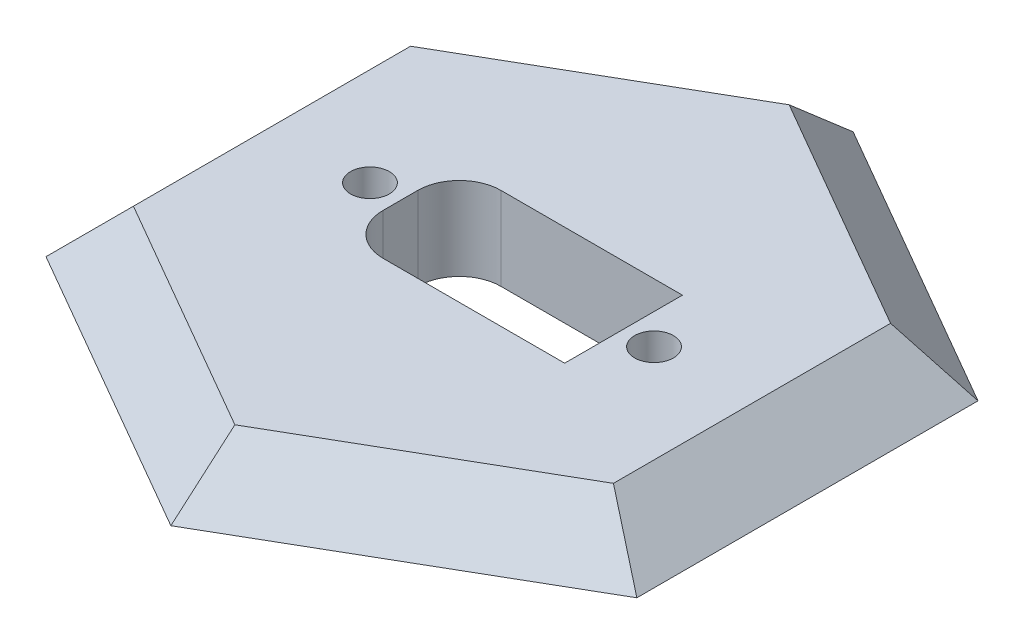
SolidWorks part; units mm, degrees
ref_plane "Płaszczyzna przednia" through (0, 0, 0) normal (0, 0, 1) x (1, 0, 0)
ref_plane "Płaszczyzna górna" through (0, 0, 0) normal (0, 1, 0) x (1, 0, 0)
ref_plane "Płaszczyzna prawa" through (0, 0, 0) normal (1, 0, 0) x (0, 0, -1)
sketch "Sketch1" plane through (0, 0, 0) normal (0, 1, 0) x (1, 0, 0)
  circle A0 centre (0, 0) radius 26
extrude "Boss-Extrude1" add sketch "Sketch1" along normal blind 4
sketch "Sketch3" plane through (0, 0, 0) normal (0, -1, 0) x (1, 0, 0)
  circle A0 centre (0, 0) radius 17
extrude "Boss-Extrude2" add sketch "Sketch3" along normal blind 2
sketch "Sketch2" plane through (0, 4, 0) normal (0, 1, 0) x (1, 0, 0)
  line L1 (-5.05, -4.25) -> (8.05, -4.25)
  line L2 (-8.05, -1.25) -> (-8.05, 1.25)
  line L3 (-5.05, 4.25) -> (8.05, 4.25)
  line L4 (8.05, -4.25) -> (8.05, 4.25)
  line L5 (-8.05, -4.25) -> (8.05, 4.25) construction
  line L6 (-8.05, 4.25) -> (8.05, -4.25) construction
  arc A0 (-5.05, -4.25) -> (-8.05, -1.25) centre (-5.05, -1.25) cw
  arc A1 (-8.05, 1.25) -> (-5.05, 4.25) centre (-5.05, 1.25) cw
  point P0 (0, 0)
  dimension "D3" = 3
  dimension "D1" = 8.5
  dimension "D2" = 16.1
extrude "Cut-Extrude1" cut sketch "Sketch2" against normal blind 20
sketch "Sketch4" plane through (0, 4, 0) normal (0, 1, 0) x (1, 0, 0)
  line L0 (0, 0) -> (-10.25, 0) construction
  line L1 (0, 0) -> (10.25, 0) construction
  circle A0 centre (-10.25, 0) radius 1.4
  circle A1 centre (10.25, 0) radius 1.4
extrude "Cut-Extrude2" cut sketch "Sketch4" against normal blind 10
sketch "Sketch6" plane through (0, 4, 0) normal (0, 1, 0) x (1, 0, 0)
  line L1 (0, 20) -> (-17.3205, 10)
  line L2 (-17.3205, 10) -> (-17.3205, -10)
  line L3 (-17.3205, -10) -> (0, -20)
  line L4 (0, -20) -> (17.3205, -10)
  line L5 (17.3205, -10) -> (17.3205, 10)
  line L6 (17.3205, 10) -> (0, 20)
  circle A0 centre (0, 0) radius 20 construction
  circle A1 centre (0, 0) radius 17.3205 construction
extrude "Cut-Extrude3" cut sketch "Sketch6" against normal blind 10 draft 45 flip side to cut
